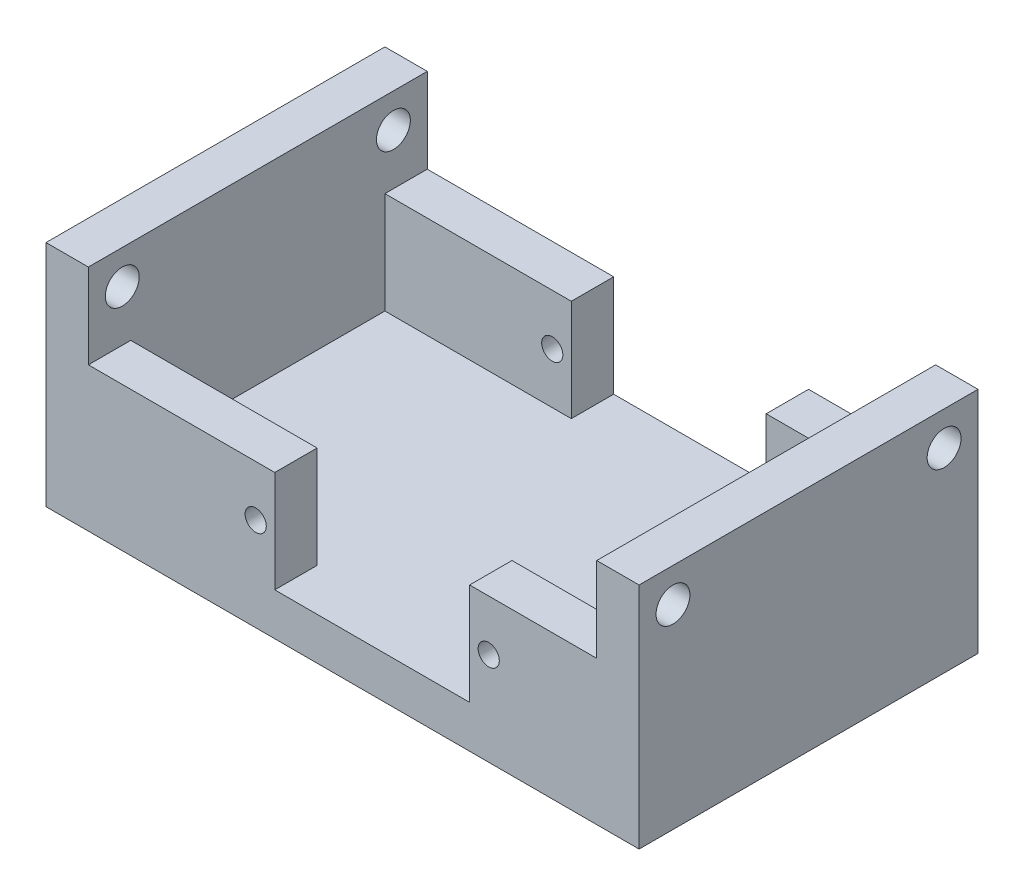
SolidWorks part; units mm, degrees
ref_plane "Front Plane" through (0, 0, 0) normal (0, 0, 1) x (1, 0, 0)
ref_plane "Top Plane" through (0, 0, 0) normal (0, 1, 0) x (1, 0, 0)
ref_plane "Right Plane" through (0, 0, 0) normal (1, 0, 0) x (0, 0, -1)
sketch "Sketch1" plane through (0, 0, 0) normal (0, 1, 0) x (1, 0, 0)
  line L1 (-35, -20) -> (35, -20)
  line L2 (-35, -20) -> (-35, 20)
  line L3 (-35, 20) -> (35, 20)
  line L4 (35, -20) -> (35, 20)
  line L5 (-35, -20) -> (35, 20) construction
  line L6 (-35, 20) -> (35, -20) construction
  point P0 (0, 0)
  dimension "D1" = 70
  dimension "D2" = 40
extrude "Boss-Extrude1" add sketch "Sketch1" along normal blind 5
sketch "Sketch2" plane through (0, 5, 0) normal (0, 1, 0) x (1, 0, 0)
  line L0 (-8, -20) -> (-8, -15)
  line L1 (-35, -20) -> (35, -20) construction
  line L2 (-8, -15) -> (-30, -15)
  line L3 (-35, 20) -> (-35, -20) construction
  line L4 (-30, -15) -> (-30, 15)
  line L6 (-30, 15) -> (-8, 15)
  line L7 (-8, 15) -> (-8, 20)
  line L8 (35, 20) -> (-35, 20) construction
  line L9 (-8, 20) -> (-35, 20)
  line L10 (-35, 20) -> (-35, -20)
  line L11 (-35, -20) -> (-8, -20)
  line L12 (15, -15) -> (30, -15)
  line L13 (35, -20) -> (35, 20) construction
  line L14 (30, -15) -> (30, 15)
  line L15 (30, 15) -> (15, 15)
  line L16 (15, 15) -> (15, 20)
  line L17 (15, 20) -> (35, 20)
  line L18 (35, 20) -> (35, -20)
  line L19 (35, -20) -> (15, -20)
  line L20 (15, -20) -> (15, -15)
  dimension "D1" = 22
  dimension "D2" = 5
  dimension "D3" = 30
  dimension "D4" = 5
  dimension "D5" = 22
  dimension "D6" = 20
  dimension "D7" = 15
  dimension "D8" = 5
  dimension "D9" = 5
extrude "Boss-Extrude2" add sketch "Sketch2" along normal blind 12
sketch "Sketch3" plane through (0, 17, 0) normal (0, 1, 0) x (1, 0, 0)
  line L0 (35, 20) -> (15, 20) construction
  line L1 (35, -20) -> (30, -20)
  line L2 (35, -20) -> (35, 20)
  line L3 (35, 20) -> (30, 20)
  line L4 (30, -20) -> (30, 20)
  line L5 (30, 15) -> (30, -15) construction
  line L6 (-35, -20) -> (-8, -20) construction
  line L7 (-35, 20) -> (-30, 20)
  line L8 (-35, 20) -> (-35, -20)
  line L9 (-35, -20) -> (-30, -20)
  line L10 (-30, 20) -> (-30, -20)
  line L11 (-30, -15) -> (-30, 15) construction
extrude "Boss-Extrude3" add sketch "Sketch3" along normal blind 10
sketch "Sketch5" plane through (-35, 0, 0) normal (-1, 0, 0) x (0, 0, 1)
  line L0 (-20, 27) -> (20, 27) construction
  line L1 (20, 27) -> (20, 0) construction
  line L2 (0, -14.85) -> (0, 14.85) construction
  circle A0 centre (16, 23) radius 2
  circle A1 centre (-16, 23) radius 2
  dimension "D1" = 4
  dimension "D2" = 4
  dimension "D3" = 4
extrude "Cut-Extrude1" cut sketch "Sketch5" against normal through all
sketch "Sketch6" plane through (0, 0, 15) normal (0, 0, -1) x (-1, 0, 0)
  circle A0 centre (10.25, 11) radius 1.25
  circle A1 centre (-17.25, 11) radius 1.25
  dimension "D1" = 2.5
extrude "Cut-Extrude2" cut sketch "Sketch6" against normal through all and the other way through all
